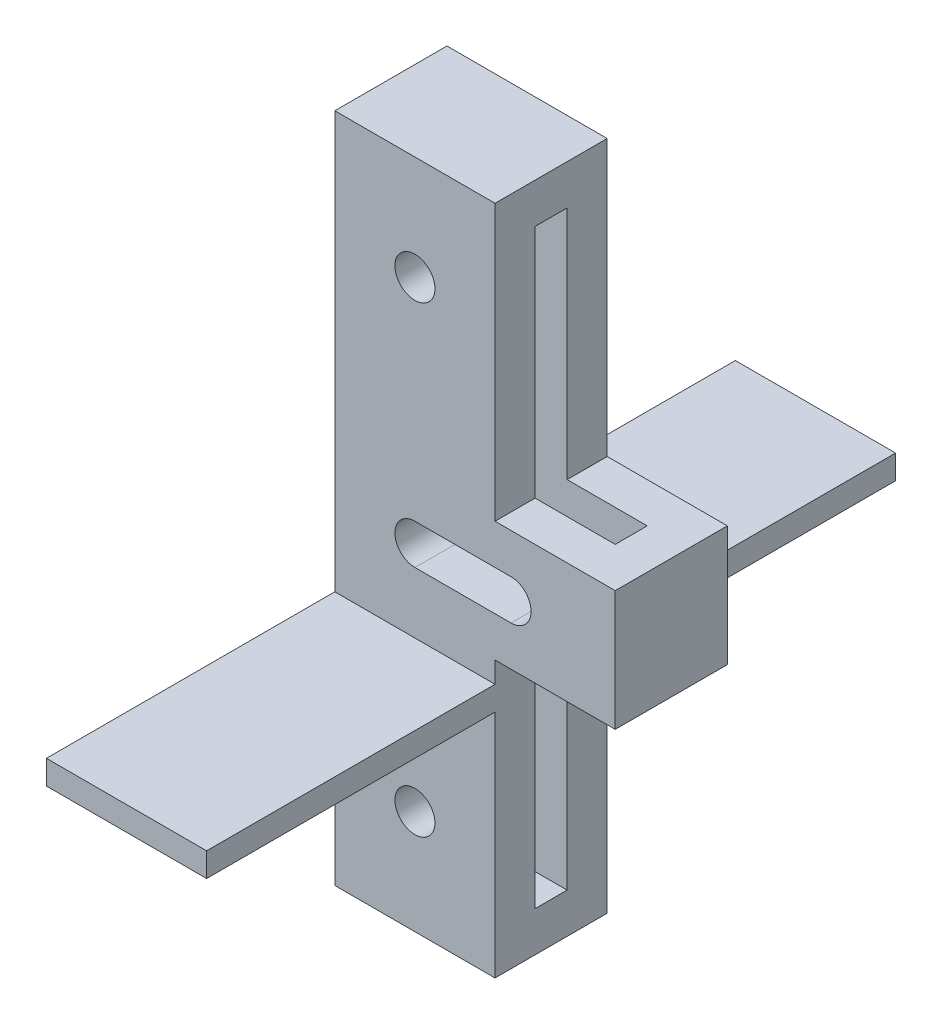
SolidWorks part; units mm, degrees
material "1060 Alloy"
ref_plane "Front Plane" through (0, 0, 0) normal (0, 0, 1) x (1, 0, 0)
ref_plane "Top Plane" through (0, 0, 0) normal (0, 1, 0) x (1, 0, 0)
ref_plane "Right Plane" through (0, 0, 0) normal (1, 0, 0) x (0, 0, -1)
sketch "Sketch1" plane through (0, 0, 0) normal (1, 0, 0) x (0, 0, -1)
  line L0 (-7, 7.5) -> (-2, 7.5)
  line L1 (-7, -41.875) -> (7, -41.875)
  line L2 (-7, -41.875) -> (-7, 41.875)
  line L3 (-7, 41.875) -> (7, 41.875)
  line L4 (7, -41.875) -> (7, 41.875)
  line L5 (-2, 7.5) -> (2, 7.5)
  line L6 (2, 7.5) -> (7, 7.5)
  line L7 (-2, 36.875) -> (2, 36.875)
  line L8 (-2, 36.875) -> (-2, -36.875)
  line L9 (-2, -36.875) -> (2, -36.875)
  line L10 (2, 36.875) -> (2, -36.875)
  line L11 (-7, -7.5) -> (-2, -7.5)
  line L12 (-2, -7.5) -> (2, -7.5)
  line L13 (43, -13.125) -> (7, -13.125)
  line L14 (43, -13.125) -> (43, -10.125)
  line L15 (43, -10.125) -> (7, -10.125)
  line L16 (7, -13.125) -> (7, -10.125)
  line L17 (43, -13.125) -> (7, -10.125) construction
  line L18 (43, -10.125) -> (7, -13.125) construction
  line L19 (-43, -13.125) -> (-7, -13.125)
  line L20 (-43, -13.125) -> (-43, -10.125)
  line L21 (-43, -10.125) -> (-7, -10.125)
  line L22 (-7, -13.125) -> (-7, -10.125)
  line L23 (-43, -13.125) -> (-7, -10.125) construction
  line L24 (-43, -10.125) -> (-7, -13.125) construction
  line L25 (-7, -28.875) -> (7, -28.875) construction
  line L26 (-7, -23.875) -> (7, -23.875) construction
  line L27 (0, 23.875) -> (0, -23.875) construction
  line L28 (-7, 0) -> (7, 0) construction
  line L29 (2, -7.5) -> (7, -7.5)
  line L30 (-7, 7.5) -> (7, -7.5) construction
  line L31 (-7, 28.875) -> (7, 28.875) construction
  line L32 (-7, 23.875) -> (7, 23.875) construction
  line L33 (-7, 33.875) -> (7, 33.875) construction
  line L34 (-7, -33.875) -> (7, -33.875) construction
  point P11 (25, -11.625)
  point P16 (-25, -11.625)
  point P34 (0, 0)
  point P40 (0, 0)
  point P45 (0, -33.875)
  point P46 (0, 33.875)
  dimension "D1" = 4
  dimension "D2" = 5
  dimension "D3" = 86
  dimension "D4" = 3
  dimension "D5" = 5
  dimension "D6" = 15.75
  dimension "D7" = 5
  dimension "D10" = 42
  dimension "D11" = 5
  dimension "D12" = 8
  dimension "D8" = 5
  dimension "D13" = 15
  dimension "D9" = 5
  dimension "D14" = 8
  dimension "D15" = 5
  dimension "D16" = 5
extrude "Boss-Extrude5" add sketch "Sketch1" along normal blind 10 and the other way blind 10 contours L7 L10 L6 L4 L3 L2 L0 L8 region at (0, 24.6875, 6.6288)
extrude "Boss-Extrude6" add sketch "Sketch1<8>" along normal blind 25 and the other way blind 10 contours L2 L11 L8 L0 | L10 L29 L4 L6 region at (0, 0, 4.5) region at (0, 0, -4.5)
sketch "Sketch1<8>" plane through (0, 0, 0) normal (1, 0, 0) x (0, 0, -1) same geometry as "Sketch1"
extrude "Boss-Extrude7" add sketch "Sketch1<9>" along normal blind 5 from offset 20 contours L8 L12 L10 L5 region at (0, 0, 0)
sketch "Sketch1<9>" plane through (0, 0, 0) normal (1, 0, 0) x (0, 0, -1) same geometry as "Sketch1"
extrude "Boss-Extrude8" add sketch "Sketch1<10>" along normal blind 10 and the other way blind 10 contours L29 L10 L9 L8 L11 L2 L1 L4 region at (0, -7.8712, 4.5)
sketch "Sketch1<10>" plane through (0, 0, 0) normal (1, 0, 0) x (0, 0, -1) same geometry as "Sketch1"
extrude "Boss-Extrude9" add sketch "Sketch1<11>" along normal blind 10 and the other way blind 10 contours L14 L15 L4 L13 | L21 L20 L19 L2 region at (0, -11.625, 25) region at (0, -11.625, -25)
sketch "Sketch1<11>" plane through (0, 0, 0) normal (1, 0, 0) x (0, 0, -1) same geometry as "Sketch1"
sketch "Sketch2" plane through (0, 0, 7) normal (0, 0, 1) x (1, 0, 0)
  line L0 (0, 0) -> (12, 0) construction
  line L1 (0, 2.5) -> (12, 2.5)
  line L2 (0, -2.5) -> (12, -2.5)
  line L3 (25, -7.5) -> (25, 7.5) construction
  line L4 (0, 0) -> (0, 42.875) construction
  line L7 (-10, -13.125) -> (10, -13.125) construction
  arc A0 (0, 2.5) -> (0, -2.5) centre (0, 0) ccw
  arc A1 (12, -2.5) -> (12, 2.5) centre (12, 0) ccw
  circle A2 centre (0, 28.875) radius 2.5
  circle A3 centre (0, -28.875) radius 2.5
  point P3 (6, 0)
  dimension "D5" = 5
  dimension "D6" = 15.75
  dimension "D3" = 5
  dimension "D1" = 5
  dimension "D2" = 13
  dimension "D4" = 42
extrude "Cut-Extrude2" cut sketch "Sketch2" against normal through all both and the other way through all
ref_point "CableCentre1"
ref_point "CableCentre2"
equation "\"CableDiameter\"= 2"
equation "\"D1@Sketch1\" = 2 + \"CableDiameter\""
equation "\"StrutWidth\"= 15"
equation "\"CarriageWidth\"= 56"
equation "\"D3@Sketch1\"=\"CarriageWidth\"+\"StrutWidth\"*2"
equation "\"StrutHeight\"= 31.5"
equation "\"D6@Sketch1\"= \"StrutHeight\" / 2"
equation "\"PulleyRadius\"=5"
equation "\"D7@Sketch1\"=\"PulleyRadius\""
equation "\"D11@Sketch1\"=\"PulleyRadius\""
equation "\"D6@Sketch2\"=\"StrutHeight\"/2"
equation "\"SpringOuterDiameter\"= 80"
equation "\"D10@Sketch1\"=\"SpringOuterDiameter\"/2+2"
equation "\"D4@Sketch2\"=\"SpringOuterDiameter\"/2+2"
equation "\"D15@Sketch1\"=\"PulleyRadius\""
equation "\"D16@Sketch1\"=\"PulleyRadius\""
